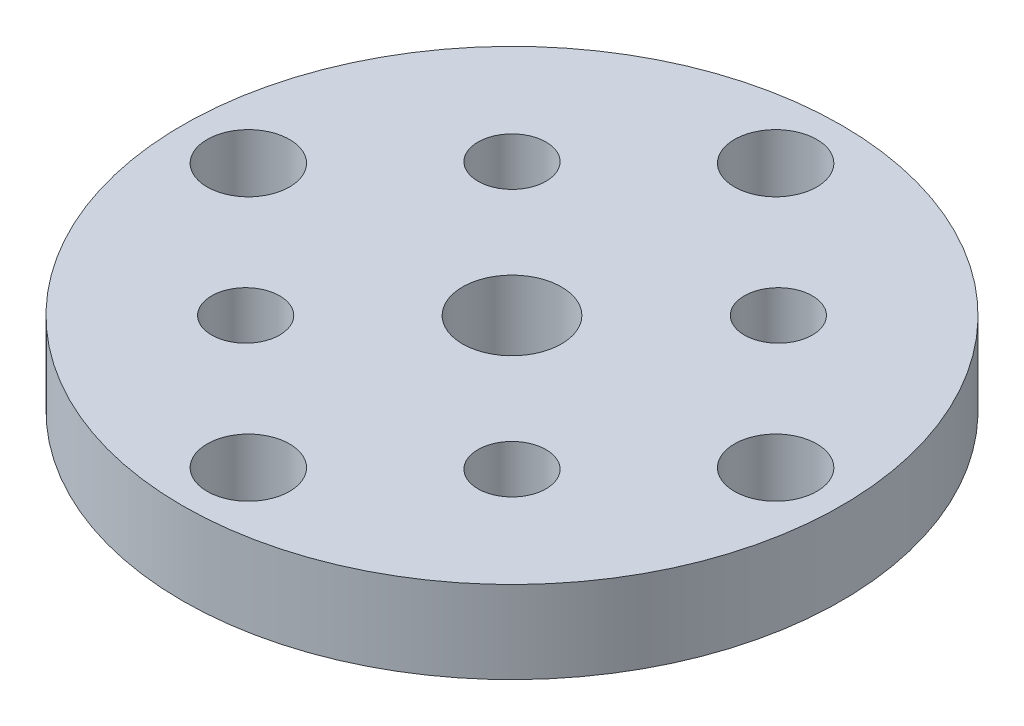
SolidWorks part; units mm, degrees
material "ABS"
ref_plane "Front Plane" through (0, 0, 0) normal (0, 0, 1) x (1, 0, 0)
ref_plane "Top Plane" through (0, 0, 0) normal (0, 1, 0) x (1, 0, 0)
ref_plane "Right Plane" through (0, 0, 0) normal (1, 0, 0) x (0, 0, -1)
sketch "Sketch1" plane through (0, 0, 0) normal (0, 1, 0) x (1, 0, 0)
  line L0 (0, 24.1217) -> (0, -25.5168) construction
  line L1 (-33.1168, 0) -> (38.4772, 0) construction
  circle A0 centre (0, 0) radius 10
  circle A1 centre (0, 0) radius 1.5
  circle A2 centre (0, 8) radius 1.25
  circle A3 centre (0, 0) radius 10
  circle A4 centre (8, 0) radius 1.25
  circle A5 centre (0, 0) radius 10
  circle A6 centre (0, -8) radius 1.25
  circle A7 centre (0, 0) radius 10
  circle A8 centre (-8, 0) radius 1.25
  point P22 (0, 0)
  dimension "D1" = 20
  dimension "D2" = 3
  dimension "D3" = 2.5
  dimension "D5" = 8
  dimension "D4" = 4
extrude "Boss-Extrude1" add sketch "Sketch1" along normal blind 2.5 contours A0 A8 A6 A4 A2 A1 region at (-9.7172, 0, 0)
cosmetic thread "Cosmetic Thread1" parameters "D1"=2.4999, "D2"=3
cosmetic thread "Cosmetic Thread2" parameters "D1"=2.4999, "D2"=3
cosmetic thread "Cosmetic Thread3" parameters "D1"=2.4999, "D2"=3
cosmetic thread "Cosmetic Thread4" parameters "D1"=2.4999, "D2"=3
sketch "Sketch2" plane through (0, 2.5, 0) normal (0, 1, 0) x (1, 0, 0)
  line L0 (-10.1496, 10.1496) -> (11.2798, -11.2798) construction
  line L1 (10.8654, 10.8654) -> (-10.8654, -10.8654) construction
  line L2 (0, 10.6288) -> (0, -11.3901) construction
  circle A0 centre (0, 0) radius 5.715 construction
  circle A1 centre (-4.0411, 4.0411) radius 1.0325
  circle A2 centre (4.0411, 4.0411) radius 1.0325
  circle A3 centre (4.0411, -4.0411) radius 1.0325
  circle A4 centre (-4.0411, -4.0411) radius 1.0325
  point P17 (-4.0411, 4.0411)
  point P18 (4.0411, 4.0411)
  point P19 (4.0411, -4.0411)
  point P20 (-4.0411, -4.0411)
  dimension "D1" = 11.43
  dimension "D3" = 2.065
  dimension "D2" = 45
extrude "Cut-Extrude1" cut sketch "Sketch2" against normal through all
